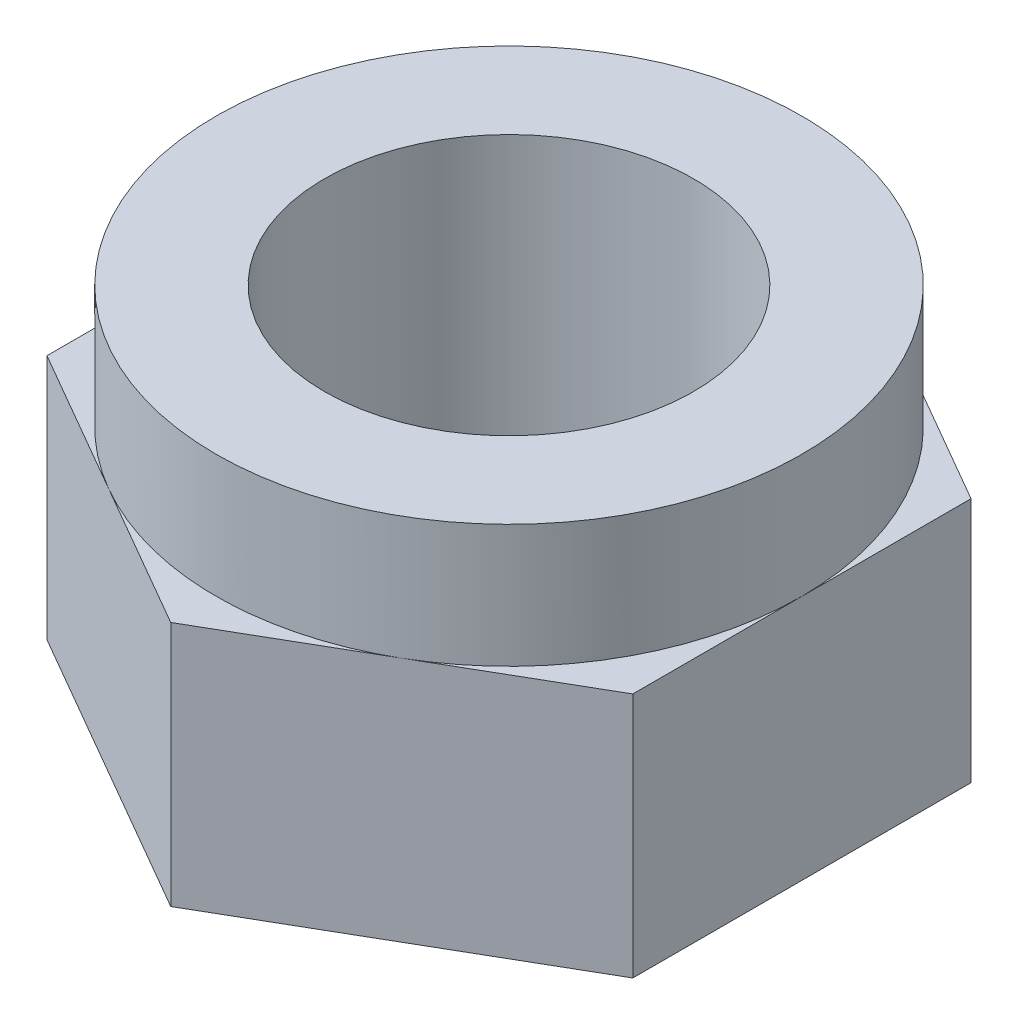
SolidWorks part; units mm, degrees
material "Stainless Steel (ferritic)"
ref_plane "Front Plane" through (0, 0, 0) normal (0, 0, 1) x (1, 0, 0)
ref_plane "Top Plane" through (0, 0, 0) normal (0, 1, 0) x (1, 0, 0)
ref_plane "Right Plane" through (0, 0, 0) normal (1, 0, 0) x (0, 0, -1)
sketch "Sketch1" plane through (0, 0, 0) normal (0, 1, 0) x (1, 0, 0)
  line L1 (0, 5.5) -> (-4.7631, 2.75)
  line L2 (-4.7631, 2.75) -> (-4.7631, -2.75)
  line L3 (-4.7631, -2.75) -> (0, -5.5)
  line L4 (0, -5.5) -> (4.7631, -2.75)
  line L5 (4.7631, -2.75) -> (4.7631, 2.75)
  line L6 (4.7631, 2.75) -> (0, 5.5)
  circle A0 centre (0, 0) radius 3
  circle A1 centre (0, 0) radius 4.7631 construction
  point P3 (5.1962, -2.4883)
  point P11 (0, 0)
  point P12 (0, 0)
  dimension "D1" = 6
  dimension "D2" = 11
extrude "Boss-Extrude1" add sketch "Sketch1" along normal blind 4
sketch "Sketch2" plane through (0, 4, 0) normal (0, 1, 0) x (1, 0, 0)
  line L0 (0, 5.5) -> (-4.7631, 2.75) construction
  circle A0 centre (0, 0) radius 4.7631
  circle A1 centre (0, 0) radius 3 construction
  circle A2 centre (0, 0) radius 3
extrude "Boss-Extrude2" add sketch "Sketch2" along normal blind 2
